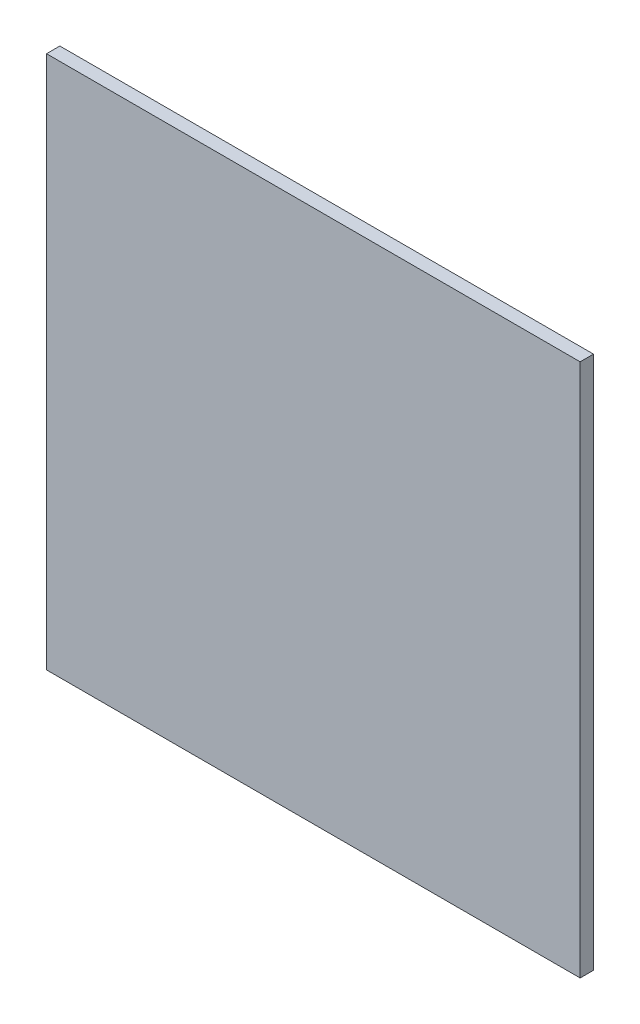
SolidWorks part; units mm, degrees
material "PVC 0.007 Plasticizado"
ref_plane "Plano frontal" through (0, 0, 0) normal (0, 0, 1) x (1, 0, 0)
ref_plane "Plano superior" through (0, 0, 0) normal (0, 1, 0) x (1, 0, 0)
ref_plane "Plano direito" through (0, 0, 0) normal (1, 0, 0) x (0, 0, -1)
sketch "Esboço1" plane through (0, 0, 0) normal (0, 0, 1) x (1, 0, 0)
  line L1 (-60, -60) -> (60, -60)
  line L2 (-60, -60) -> (-60, 60)
  line L3 (-60, 60) -> (60, 60)
  line L4 (60, -60) -> (60, 60)
  line L5 (-60, -60) -> (60, 60) construction
  line L6 (-60, 60) -> (60, -60) construction
  point P0 (0, 0)
  dimension "D1" = 120
  dimension "D2" = 120
extrude "Ressalto-extrusão1" add sketch "Esboço1" along normal blind 3
sketch "Esboço2" plane through (0, 0, 0) normal (0, 0, -1) x (-1, 0, 0)
  line L8 (-56.4, 56.4) -> (-56.4, -56.4)
  line L9 (-56.4, -56.4) -> (56.4, -56.4)
  line L10 (56.4, -56.4) -> (56.4, 56.4)
  line L11 (56.4, 56.4) -> (-56.4, 56.4)
  line L12 (-56.4, 56.4) -> (-56.4, -56.4)
  line L13 (-56.4, -56.4) -> (56.4, -56.4)
  line L14 (56.4, -56.4) -> (56.4, 56.4)
  line L15 (56.4, 56.4) -> (-56.4, 56.4)
  dimension "D1" = 3.6
extrude "Ressalto-extrusão2" add sketch "Esboço2" along normal blind 2
sketch "Esboço3" plane through (0, 0, -2) normal (0, 0, -1) x (-1, 0, 0)
  line L8 (54.4, 54.4) -> (-54.4, 54.4)
  line L9 (-54.4, 54.4) -> (-54.4, -54.4)
  line L10 (-54.4, -54.4) -> (54.4, -54.4)
  line L11 (54.4, -54.4) -> (54.4, 54.4)
  line L12 (54.4, 54.4) -> (-54.4, 54.4)
  line L13 (-54.4, 54.4) -> (-54.4, -54.4)
  line L14 (-54.4, -54.4) -> (54.4, -54.4)
  line L15 (54.4, -54.4) -> (54.4, 54.4)
  dimension "D1" = 2
extrude "Corte-extrusão1" cut sketch "Esboço3" against normal blind 2
sketch "Esboço5" plane through (0, 0, 0) normal (0, 0, -1) x (-1, 0, 0)
  line L0 (56.4, -56.4) -> (56.4, 56.4) construction
  line L1 (56.4, 56.4) -> (-56.4, 56.4) construction
  circle A0 centre (51.4, 51.4) radius 5
extrude "Ressalto-extrusão3" add sketch "Esboço5" along normal blind 2
mirror "Espelhar1" about plane through (0, 0, 0) normal (1, 0, 0) of "Ressalto-extrusão3"
mirror "Espelhar2" about plane through (0, 0, 0) normal (0, 1, 0) of "Espelhar1"
chamfer "Chanfro1" distance 0.5 angle 45 4 edges at (-56.4, 0, -2) (0, -56.4, -2) (56.4, 0, -2) (0, 56.4, -2)
fillet "Filete1" radius 2 8 edges at (0, -54.4, 0) (47.8645, -47.8645, 0) (54.4, 0, 0) (47.8645, 47.8645, 0) (0, 54.4, 0) (-47.8645, 47.8645, 0) (-54.4, 0, 0) (-47.8645, -47.8645, 0)
